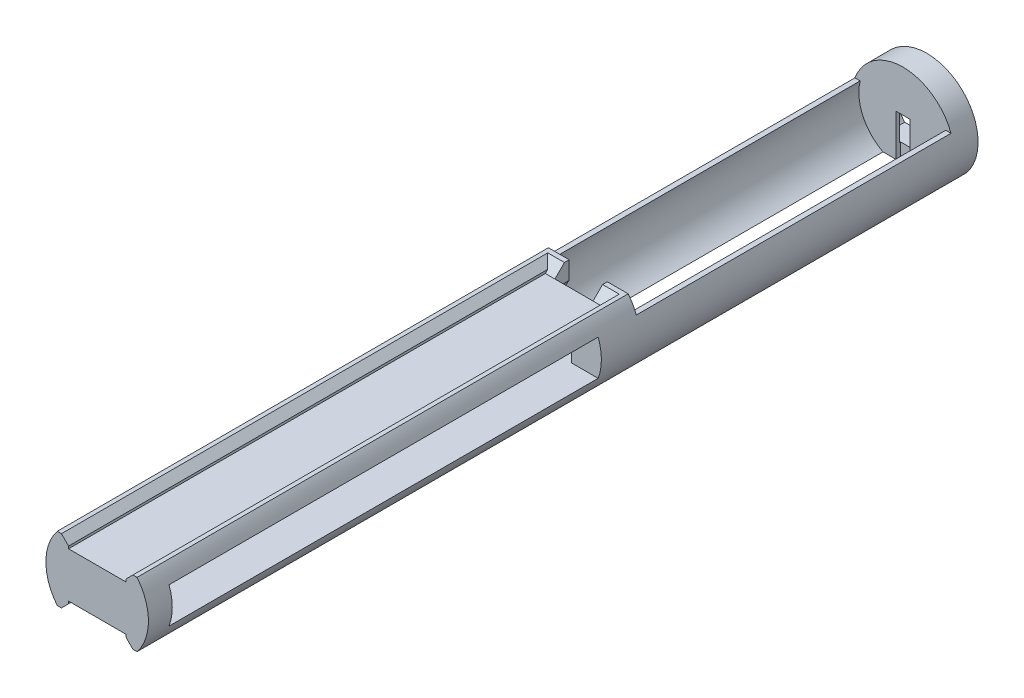
SolidWorks part; units mm, degrees
ref_plane "前基準面" through (0, 0, 0) normal (0, 0, 1) x (1, 0, 0)
ref_plane "上基準面" through (0, 0, 0) normal (0, 1, 0) x (1, 0, 0)
ref_plane "右基準面" through (0, 0, 0) normal (1, 0, 0) x (0, 0, -1)
sketch "草圖1" plane through (0, 0, 0) normal (0, 0, 1) x (1, 0, 0)
  line L2 (0, 6.5) -> (0, -6.5) construction
  line L3 (-10.0747, 3.75) -> (10.0747, 3.75) construction
  line L5 (-10.0747, -3.75) -> (10.0747, -3.75) construction
  line L6 (10.0747, 3.75) -> (10.0747, -3.75) construction
  line L8 (-6, 5.25) -> (-6, 4.75)
  line L9 (-6, 4.75) -> (6, 4.75)
  line L10 (6, 5.25) -> (6, 4.75)
  line L12 (-6, -5.25) -> (-6, -4.75)
  line L13 (-6, -4.75) -> (6, -4.75)
  line L14 (6, -5.25) -> (6, -4.75)
  line L15 (-8.3666, 6.75) -> (-7.5, 6.75)
  line L16 (7.5, 6.75) -> (8.3666, 6.75)
  line L17 (-8.3666, -6.75) -> (-7.5, -6.75)
  line L18 (7.5, -6.75) -> (8.3666, -6.75)
  line L19 (-7.5, 6.75) -> (-6, 5.25)
  line L20 (6, 5.25) -> (7.5, 6.75)
  line L21 (6, -5.25) -> (7.5, -6.75)
  line L22 (-7.5, -6.75) -> (-6, -5.25)
  arc A0 (-8.3666, 6.75) -> (-10.0747, 3.75) centre (0, 0) ccw
  arc A1 (-10.0747, -3.75) -> (-8.3666, -6.75) centre (0, 0) ccw
  arc A2 (8.3666, 6.75) -> (10.0747, 3.75) centre (0, 0) cw
  arc A3 (10.0747, -3.75) -> (8.3666, -6.75) centre (0, 0) cw
  arc A4 (10.0747, -3.75) -> (10.0747, 3.75) centre (0, 0) ccw
  arc A5 (-10.0747, -3.75) -> (-10.0747, 3.75) centre (0, 0) cw
  point P11 (-6, -6.75)
  point P12 (-6, 6.75)
  point P15 (6, 6.75)
  point P18 (6, -6.75)
  point P35 (0, -4.75)
  dimension "D1" = 10.75
  dimension "D2" = 7.5
  dimension "D3" = 3
  dimension "D4" = 1
  dimension "D5" = 1
  dimension "D6" = 12
  dimension "D7" = 3
extrude "填料-伸長1" add sketch "草圖1" along normal blind 100
sketch "草圖3" plane through (0, 0, 0) normal (1, 0, 0) x (0, 0, -1)
  line L0 (0, 0) -> (-100, 0) construction
  line L1 (-5, 3.75) -> (-95, 3.75)
  line L2 (-5, 3.75) -> (-5, -3.75)
  line L3 (-5, -3.75) -> (-95, -3.75)
  line L4 (-95, 3.75) -> (-95, -3.75)
  line L5 (-100, 6.75) -> (-100, -6.75) construction
  line L6 (0, -6.75) -> (0, 6.75) construction
  point P9 (-5, 0)
  dimension "D1" = 7.5
  dimension "D2" = 90
  dimension "D3" = 5
extrude "除料-伸長1" cut sketch "草圖3" against normal blind 20 and the other way blind 20
sketch "草圖4" plane through (0, 0, 0) normal (0, 0, -1) x (-1, 0, 0)
  line L0 (-8.3666, 6.75) -> (8.3666, 6.75) construction
  line L1 (8.3666, -6.75) -> (-8.3666, -6.75) construction
  line L2 (0, 3) -> (0, -3) construction
  line L3 (-4, 6.75) -> (4, 6.75) construction
  line L4 (-4, 6.75) -> (-4, 3)
  line L5 (-4, 3) -> (4, 3) construction
  line L6 (4, 6.75) -> (4, 3)
  line L7 (4, -3) -> (-4, -3) construction
  line L8 (4, -3) -> (4, -6.75)
  line L9 (4, -6.75) -> (-4, -6.75) construction
  line L10 (-4, -3) -> (-4, -6.75)
  line L11 (-8.3666, 6.75) -> (-4, 6.75)
  line L12 (4, 6.75) -> (8.3666, 6.75)
  line L13 (-8.3666, -6.75) -> (-4, -6.75)
  line L14 (4, -6.75) -> (8.3666, -6.75)
  arc A2 (-8.3666, 6.75) -> (-8.3666, -6.75) centre (0, 0) ccw
  arc A3 (-8.3666, 6.75) -> (-8.3666, -6.75) centre (0, 0) ccw construction
  arc A4 (8.3666, -6.75) -> (8.3666, 6.75) centre (0, 0) ccw
  arc A5 (8.3666, -6.75) -> (8.3666, 6.75) centre (0, 0) ccw construction
  arc A6 (-4, 3) -> (-4, -3) centre (0, 0) ccw
  arc A8 (4, 3) -> (4, -3) centre (0, 0) cw
  point P24 (4, -2.9841)
  dimension "D1" = 5
  dimension "D2" = 8
extrude "填料-伸長2" add sketch "草圖4" along normal blind 3
sketch "草圖6" plane through (0, 0, -3) normal (0, 0, -1) x (-1, 0, 0)
  line L0 (0, 0) -> (0, 10.75) construction
  line L1 (-8.3666, -6.75) -> (-4.1833, -6.75)
  line L3 (-10.0747, 3.75) -> (10.0747, 3.75) construction
  line L4 (4.1833, -6.75) -> (8.3666, -6.75)
  line L5 (-10.0747, 3.75) -> (-8.9722, 3.75)
  line L6 (8.9722, 3.75) -> (10.0747, 3.75)
  line L7 (-8.3666, -6.75) -> (-4, -6.75) construction
  circle A1 centre (0, 1.5) radius 9.25 construction
  arc A2 (-8.9722, 3.75) -> (-4.1833, -6.75) centre (0, 1.5) ccw
  arc A3 (4.1833, -6.75) -> (8.9722, 3.75) centre (0, 1.5) ccw
  arc A4 (-8.3666, -6.75) -> (-10.0747, 3.75) centre (0, 0) ccw construction
  arc A5 (8.3666, -6.75) -> (10.0747, 3.75) centre (0, 0) ccw
  arc A6 (-10.0747, 3.75) -> (-8.3666, -6.75) centre (0, 0) ccw
  point P8 (-8.4169, -6.6872)
  arc M9 (8.3666, -6.75) -> (8.3666, 6.75) centre (0, 0) ccw
  dimension "D1" = 18.5
  dimension "D2" = 10.5
extrude "填料-伸長3" add sketch "草圖6" along normal blind 66 contours A2 L5 | A3 L6 M9 region at (8.7873, -2.5855, -3) region at (-8.7873, -2.5855, -3)
sketch "草圖7" plane through (0, 0, 0) normal (0, 0, -1) x (-1, 0, 0)
  circle A0 centre (0, 0) radius 3.75
  dimension "D1" = 7.5
extrude "除料-伸長2" cut sketch "草圖7" against normal blind 5
chamfer "導角1" distance 2 angle 45 4 edges at (-5.75, -6.75, 0) (5.75, -6.75, 0) (5.75, 6.75, 0) (-5.75, 6.75, 0)
sketch "草圖8" plane through (0, 0, -69) normal (0, 0, -1) x (-1, 0, 0)
  line L0 (-8.3666, -6.75) -> (8.3666, -6.75)
  arc A0 (8.3666, -6.75) -> (-8.3666, -6.75) centre (0, 0) ccw
extrude "填料-伸長4" add sketch "草圖8" along normal blind 5
sketch "草圖9" plane through (0, 0, -74) normal (0, 0, -1) x (-1, 0, 0)
  line L1 (-4.65, 4.1) -> (4.65, 4.1)
  line L2 (-4.65, 4.1) -> (-4.65, -4.1) construction
  line L3 (-4.65, -4.1) -> (4.65, -4.1)
  line L4 (4.65, 4.1) -> (4.65, -4.1) construction
  line L5 (-4.65, 4.1) -> (4.65, -4.1) construction
  line L6 (-4.65, -4.1) -> (4.65, 4.1) construction
  arc A0 (4.65, -4.1) -> (4.65, 4.1) centre (0, 0) ccw
  arc A1 (-4.65, 4.1) -> (-4.65, -4.1) centre (0, 0) ccw
  point P0 (0, 0)
  dimension "D1" = 9.3
  dimension "D2" = 8.2
extrude "除料-伸長3" cut sketch "草圖9" against normal blind 4.2
sketch "草圖10" plane through (0, 0, -74) normal (0, 0, -1) x (-1, 0, 0)
  line L1 (-7.25, -6.75) -> (-5.75, -6.75)
  line L2 (-7.25, -6.75) -> (-7.25, 2.2)
  line L3 (-7.25, 2.2) -> (-5.75, 2.2)
  line L4 (-5.75, -6.75) -> (-5.75, 2.2)
  line L5 (-5.75, 0) -> (5.75, 0) construction
  line L6 (7.25, -6.75) -> (5.75, -6.75)
  line L7 (7.25, -6.75) -> (7.25, 2.2)
  line L8 (7.25, 2.2) -> (5.75, 2.2)
  line L9 (5.75, -6.75) -> (5.75, 2.2)
  line L10 (-8.3666, -6.75) -> (8.3666, -6.75) construction
  point P4 (6.7864, 1.6295)
  point P14 (0, 0)
  dimension "D1" = 1.5
  dimension "D2" = 1.5
  dimension "D3" = 11.5
  dimension "D4" = 2.2
extrude "除料-伸長4" cut sketch "草圖10" against normal blind 2
sketch "草圖11" plane through (0, 0, -69) normal (0, 0, 1) x (1, 0, 0)
  line L0 (4.1833, -6.75) -> (-4.1833, -6.75) construction
  line L1 (-1.5, -6.75) -> (1.5, -6.75)
  line L2 (-1.5, -6.75) -> (-1.5, 2)
  line L3 (-1.5, 2) -> (1.5, 2)
  line L4 (1.5, -6.75) -> (1.5, 2)
  line L5 (0, 2) -> (0, -6.75) construction
  dimension "D1" = 3
  dimension "D2" = 2
extrude "除料-伸長5" cut sketch "草圖11" against normal blind 1
sketch "草圖12" plane through (0, -3.75, 0) normal (0, 1, 0) x (1, 0, 0)
  line L0 (4.5, -5) -> (1.5, 0)
  line L1 (1.5, 0) -> (-1.5, 0)
  line L2 (-1.5, 0) -> (-4.5, -5)
  line L3 (-4.5, -5) -> (4.5, -5)
  line L4 (0, 0) -> (0, -5) construction
  line L5 (0, -5) -> (-10.0747, -5) construction
  point P7 (-4.1606, -5.2488)
  point P8 (0, -5)
  point P9 (0, 0)
  point P10 (1.9701, -1.9598)
  dimension "D1" = 5
  dimension "D2" = 3
  dimension "D3" = 9
extrude "除料-伸長6" cut sketch "草圖12" along normal blind 7.5
